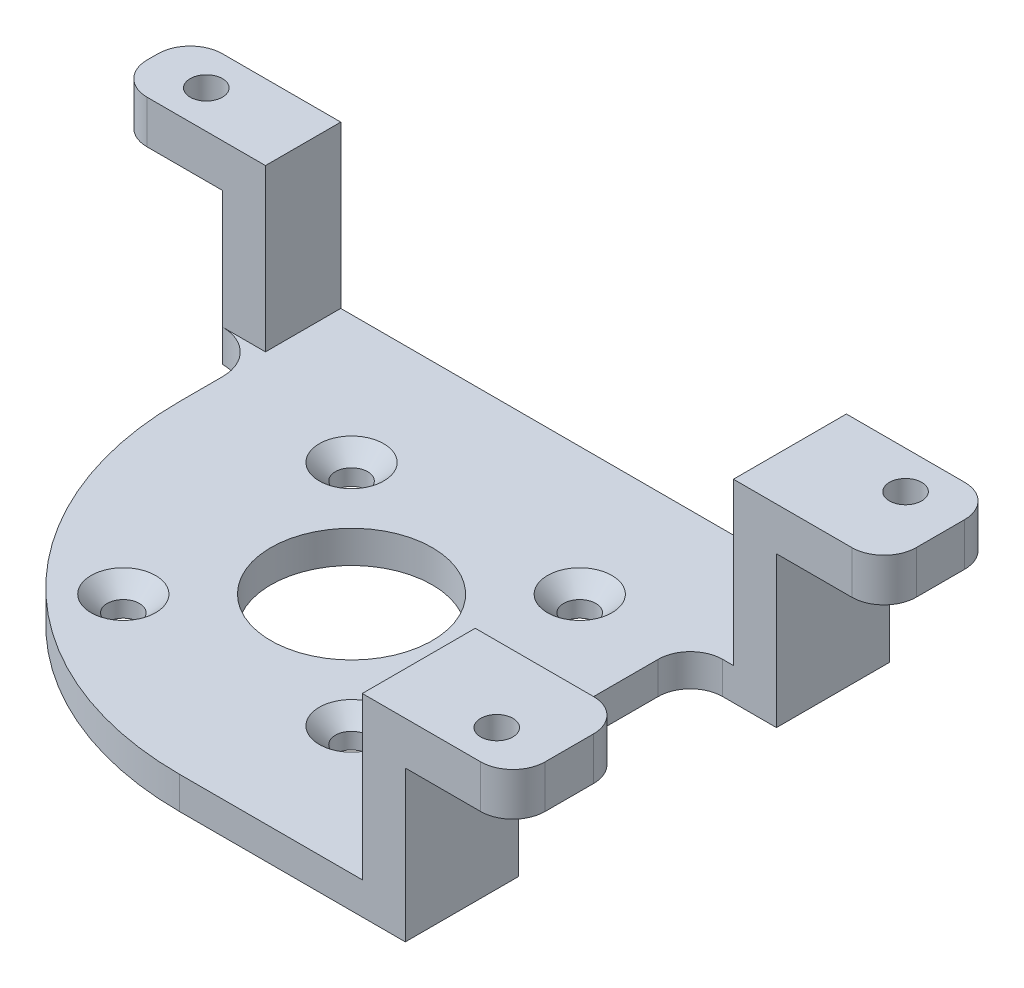
SolidWorks part; units mm, degrees
material "6061 合金"
ref_plane "前视基准面" through (0, 0, 0) normal (0, 0, 1) x (1, 0, 0)
ref_plane "上视基准面" through (0, 0, 0) normal (0, 1, 0) x (1, 0, 0)
ref_plane "右视基准面" through (0, 0, 0) normal (1, 0, 0) x (0, 0, -1)
sketch "草图1" plane through (0, 0, 0) normal (0, 1, 0) x (1, 0, 0)
  line L1 (-37.5, 22.5) -> (37.5, 22.5)
  line L2 (-37.5, 22.5) -> (-37.5, -22.5)
  line L3 (-37.5, -22.5) -> (37.5, -22.5)
  line L4 (37.5, 22.5) -> (37.5, -22.5)
  line L5 (-37.5, 22.5) -> (37.5, -22.5) construction
  line L6 (-37.5, -22.5) -> (37.5, 22.5) construction
  point P0 (0, 0)
  dimension "D1" = 45
  dimension "D2" = 75
extrude "凸台-拉伸1" add sketch "草图1" along normal blind 18
sketch "草图2" plane through (0, 0, 0) normal (0, -1, 0) x (1, 0, 0)
  line L0 (37.5, -22.5) -> (-37.5, -22.5) construction
  line L1 (-37.5, 22.5) -> (-27.5, 22.5)
  line L2 (-37.5, 22.5) -> (-37.5, -22.5)
  line L3 (-37.5, -22.5) -> (-27.5, -22.5)
  line L4 (-27.5, 22.5) -> (-27.5, -22.5)
  line L5 (0, -22.5) -> (0, 22.5) construction
  line L6 (-37.5, 22.5) -> (37.5, 22.5) construction
  line L7 (37.5, -22.5) -> (27.5, -22.5)
  line L8 (27.5, 22.5) -> (27.5, -22.5)
  line L9 (37.5, 22.5) -> (27.5, 22.5)
  line L10 (37.5, 22.5) -> (37.5, -22.5)
  dimension "D1" = 10
extrude "切除-拉伸1" cut sketch "草图2" against normal blind 14
sketch "草图3" plane through (0, 18, 0) normal (0, 1, 0) x (1, 0, 0)
  line L0 (37.5, 22.5) -> (-37.5, 22.5) construction
  line L1 (-23.5, -22.5) -> (23.5, -22.5)
  line L2 (-23.5, -22.5) -> (-23.5, 22.5)
  line L3 (-23.5, 22.5) -> (23.5, 22.5)
  line L4 (23.5, -22.5) -> (23.5, 22.5)
  line L5 (-23.5, -22.5) -> (23.5, 22.5) construction
  line L6 (-23.5, 22.5) -> (23.5, -22.5) construction
  point P0 (0, 0)
  dimension "D1" = 47
extrude "切除-拉伸2" cut sketch "草图3" against normal blind 15
sketch "草图4" plane through (0, 0, 0) normal (0, -1, 0) x (1, 0, 0)
  line L0 (0, 15) -> (0, 0) construction
  line L1 (0, 0) -> (10.6066, 10.6066) construction
  circle A0 centre (0, 0) radius 15 construction
  circle A1 centre (10.6066, 10.6066) radius 1.5
  circle A2 centre (10.6066, -10.6066) radius 1.5
  circle A3 centre (-10.6066, -10.6066) radius 1.5
  circle A4 centre (-10.6066, 10.6066) radius 1.5
  circle A5 centre (0, 0) radius 7.5
  point P15 (0, 0)
  dimension "D1" = 30
  dimension "D3" = 3
  dimension "D5" = 15
  dimension "D2" = 45
  dimension "D4" = 4
extrude "切除-拉伸3" cut sketch "草图4" against normal through all
sketch "草图5" plane through (0, 18, 0) normal (0, 1, 0) x (1, 0, 0)
  line L5 (37.5, -22.5) -> (37.5, 22.5) construction
  line L6 (23.5, -22.5) -> (37.5, -22.5)
  line L7 (23.5, -22.5) -> (23.5, 15.5)
  line L8 (23.5, 15.5) -> (37.5, 15.5)
  line L9 (37.5, -22.5) -> (37.5, 15.5)
  dimension "D2" = 38
extrude "切除-拉伸4" cut sketch "草图5" against normal through all
fillet "圆角1" radius 30 1 edges at (23.5, 1.5, 22.5)
chamfer "倒角1" distance 1.5 angle 45 4 edges at (-10.6066, 3, 9.1066) (-10.6066, 3, -12.1066) (10.6066, 3, -12.1066) (10.6066, 3, 9.1066)
sketch "草图8" plane through (0, 0, 0) normal (0, -1, 0) x (1, 0, 0)
  line L0 (0, 0) -> (-37.5, 0) construction
  line L1 (-37.5, 22.5) -> (-37.5, -22.5) construction
  line L3 (-19.5, -12) -> (-55.5, -12)
  line L4 (-19.5, -12) -> (-19.5, 12)
  line L5 (-19.5, 12) -> (-55.5, 12)
  line L6 (-55.5, -12) -> (-55.5, 12)
  line L7 (-19.5, -12) -> (-55.5, 12) construction
  line L8 (-19.5, 12) -> (-55.5, -12) construction
  dimension "D1" = 24
  dimension "D2" = 18
extrude "切除-拉伸6" cut sketch "草图8" against normal through all
fillet "圆角2" radius 3 2 edges at (-19.5, 1.5, -12) (-19.5, 1.5, 12)
sketch "草图9" plane through (0, 14, 0) normal (0, -1, 0) x (1, 0, 0)
  line L0 (27.5, -22.5) -> (37.5, -22.5) construction
  line L1 (32.5, -19) -> (-32.5, -19) construction
  line L2 (32.5, -19) -> (32.5, 19) construction
  line L3 (32.5, 19) -> (-32.5, 19) construction
  line L4 (-32.5, -19) -> (-32.5, 19) construction
  line L5 (32.5, -19) -> (-32.5, 19) construction
  line L6 (32.5, 19) -> (-32.5, -19) construction
  line L7 (37.5, -22.5) -> (37.5, -15.5) construction
  circle A0 centre (32.5, -19) radius 1.5
  circle A1 centre (-32.5, -19) radius 1.5
  circle A2 centre (-32.5, 19) radius 1.5
  point P0 (0, 0)
  dimension "D3" = 3
  dimension "D4" = 3
  dimension "D5" = 3
  dimension "D1" = 3.5
  dimension "D2" = 5
extrude "切除-拉伸7" cut sketch "草图9" against normal through all
fillet "圆角3" radius 3 6 edges at (37.5, 16, -15.5) (37.5, 16, -22.5) (-37.5, 16, -12) (-37.5, 16, -22.5) (-37.5, 16, 22.5) (-37.5, 16, 12)
fillet "圆角4" radius 4 1 edges at (23.5, 1.5, -15.5)
ref_plane "基准面1" through (-47.5, 0, 0) normal (-1, 0, 0) x (0, 0, 1)
mirror "镜向1" about plane through (-47.5, 0, 0) normal (-1, 0, 0) of bodies 114
sketch "草图10" plane through (0, 0, 0) normal (0, -1, 0) x (1, 0, 0)
  line L1 (-46.9446, 40.0796) -> (66.5371, 40.0796)
  line L2 (-46.9446, 40.0796) -> (-46.9446, -41.3755)
  line L3 (-46.9446, -41.3755) -> (66.5371, -41.3755)
  line L4 (66.5371, 40.0796) -> (66.5371, -41.3755)
extrude "切除-拉伸9" cut sketch "草图10" against normal through all
